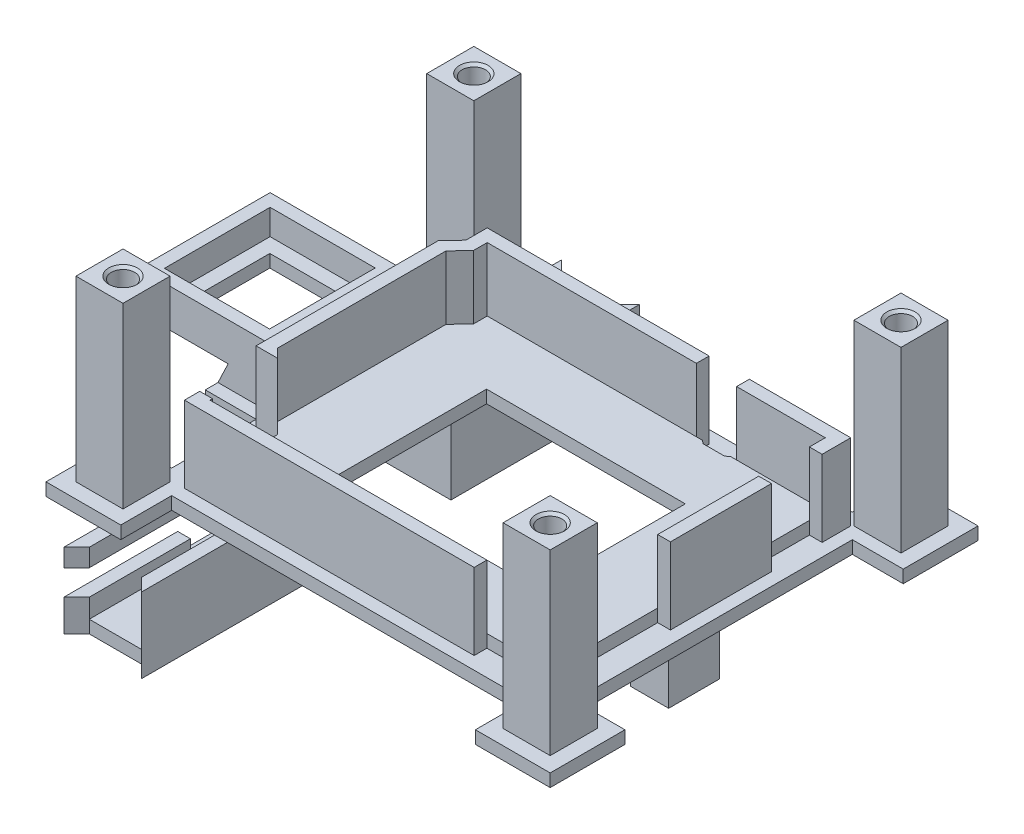
SolidWorks part; units mm, degrees
ref_plane "Front Plane" through (0, 0, 0) normal (0, 0, 1) x (1, 0, 0)
ref_plane "Top Plane" through (0, 0, 0) normal (0, 1, 0) x (1, 0, 0)
ref_plane "Right Plane" through (0, 0, 0) normal (1, 0, 0) x (0, 0, -1)
sketch "Sketch1" plane through (0, 0, 0) normal (0, -1, 0) x (1, 0, 0)
  line L0 (-32.325, 27.025) -> (34.525, 27.025)
  line L1 (34.525, 27.025) -> (34.525, -27.025)
  line L2 (34.525, -27.025) -> (-31.895, -27.025)
  line L3 (-31.895, -27.025) -> (-31.895, -24.3396)
  line L4 (-31.895, -24.3396) -> (-34.525, -21.5496)
  line L5 (-34.525, -21.5496) -> (-34.525, 11.501)
  line L6 (-34.525, 11.501) -> (-32.325, 13.751)
  line L7 (-32.325, 13.751) -> (-32.325, 27.025)
  line L8 (-32.2, 26.9) -> (34.4, 26.9) construction
  line L9 (34.4, -26.9) -> (34.4, 26.9) construction
  line L10 (16.6, -26.9) -> (34.4, -26.9) construction
  line L11 (-32.2, 13.7) -> (-32.2, 26.9) construction
  line L12 (-34.4, 11.45) -> (-32.2, 13.7) construction
  line L13 (-34.4, -21.5) -> (-34.4, 11.45) construction
  line L14 (-27.4777, 29.525) -> (37.025, 29.525)
  line L15 (37.025, 29.525) -> (37.025, -29.525)
  line L16 (37.025, -29.525) -> (-34.395, -29.525)
  line L17 (-31.77, -24.29) -> (-31.77, -26.9) construction
  line L18 (-34.4, -21.5) -> (-31.77, -24.29) construction
  line L19 (-34.395, -29.525) -> (-34.395, -25.3322)
  line L20 (-34.395, -25.3322) -> (-37.025, -22.5422)
  line L21 (-37.025, -22.5422) -> (-37.025, 14.001)
  line L22 (-37.025, 14.001) -> (-34.825, 16.251)
  line L23 (-34.825, 16.251) -> (-34.825, 29.525)
  line L24 (-34.825, 29.525) -> (-27.4777, 29.525)
  line L25 (-32.325, 26.525) -> (-34.825, 26.525)
  line L26 (9.2, -27.025) -> (17.1, -27.025)
  line L27 (9.2, -27.025) -> (9.2, -29.525)
  line L28 (9.2, -29.525) -> (17.1, -29.525)
  line L29 (17.1, -27.025) -> (17.1, -29.525)
  line L30 (-32.8139, 13.251) -> (-37.025, 13.251)
  line L32 (38.01, -14.45) -> (34.4, -14.45) construction
  line L33 (34.525, -23.9) -> (37.025, -23.9)
  line L34 (34.525, -23.9) -> (34.525, -13.95)
  line L35 (34.525, -13.95) -> (37.025, -13.95)
  line L36 (37.025, -23.9) -> (37.025, -13.95)
  line L37 (38.01, -23.4) -> (34.4, -23.4) construction
  line L38 (39.03, 17) -> (34.4, 17) construction
  line L39 (37.025, 17.5) -> (34.525, 17.5)
  line L40 (37.025, 17.5) -> (37.025, 5.9)
  line L41 (37.025, 5.9) -> (34.525, 5.9)
  line L42 (34.525, 17.5) -> (34.525, 5.9)
  line L43 (39.03, 6.4) -> (34.4, 6.4) construction
  line L44 (22.59, 26.9) -> (22.59, 22.54) construction
  line L46 (-32.325, 26.525) -> (-32.325, 16.751)
  line L48 (-34.825, 26.525) -> (-34.825, 16.751)
  line L49 (22.09, 29.525) -> (29.39, 29.525)
  line L50 (22.09, 29.525) -> (22.09, 27.025)
  line L51 (22.09, 27.025) -> (29.39, 27.025)
  line L52 (29.39, 29.525) -> (29.39, 27.025)
  line L53 (34.525, 24.8) -> (37.025, 24.8)
  line L54 (34.525, 24.8) -> (34.525, 16.8)
  line L55 (34.525, 16.8) -> (37.025, 16.8)
  line L56 (37.025, 24.8) -> (37.025, 16.8)
  line L57 (28.89, 26.9) -> (28.89, 22.54) construction
  line L58 (34.4, 24.3) -> (32.05, 24.3) construction
  line L59 (34.4, 17.3) -> (32.05, 17.3) construction
  line L72 (10.3667, -27.025) -> (11.0667, -26.5)
  line L73 (11.0667, -26.5) -> (15.2333, -26.5)
  line L74 (15.2333, -26.5) -> (15.9333, -27.025)
  line L75 (10.9, -26) -> (9.7, -26.9) construction
  line L77 (15.4, -26) -> (10.9, -26) construction
  line L79 (15.4, -26) -> (16.6, -26.9) construction
  point P72 (35.775, 24.8)
  line M6 (15.4, -26) -> (16.6, -26.9)
  line M7 (16.6, -26.9) -> (34.4, -26.9)
  line M8 (34.4, -26.9) -> (34.4, 26.9)
  line M9 (34.4, 26.9) -> (-32.2, 26.9)
  line M10 (-32.2, 26.9) -> (-32.2, 13.7)
  line M11 (-32.2, 13.7) -> (-34.4, 11.45)
  line M12 (-34.4, 11.45) -> (-34.4, -21.5)
  line M13 (-34.4, -21.5) -> (-31.77, -24.29)
  line M14 (-31.77, -24.29) -> (-31.77, -26.9)
  line M15 (-31.77, -26.9) -> (9.7, -26.9)
  line M16 (9.7, -26.9) -> (10.9, -26)
  line M17 (10.9, -26) -> (15.4, -26)
  dimension "D1" = 0.125
  dimension "D2" = 0.125
  dimension "D3" = 0.125
  dimension "D4" = 0.125
  dimension "D5" = 0.125
  dimension "D6" = 0.125
  dimension "D7" = 0.125
  dimension "D8" = 0.125
  dimension "D9" = 2.5
  dimension "D10" = 2.5
  dimension "D11" = 2.5
  dimension "D12" = 2.5
  dimension "D13" = 2.5
  dimension "D14" = 2.5
  dimension "D15" = 2.5
  dimension "D16" = 2.5
  dimension "D17" = 2.5
  dimension "D19" = 0.5
  dimension "D18" = 0.5
  dimension "D20" = 0.5
  dimension "D21" = 0.5
  dimension "D22" = 0.5
  dimension "D23" = 0.5
  dimension "D26" = 0.5
  dimension "D27" = 0.5
  dimension "D28" = 0.5
  dimension "D29" = 0.5
  dimension "D30" = 0.5
  dimension "D31" = 0.5
  dimension "D32" = 0.5
  dimension "D24" = 0.5
  dimension "D25" = 0.5
extrude "Boss-Extrude4" add sketch "Sketch1" along normal blind 2.5 contours L7 L23 L22 L21 L20 L19 L16 L27 L2 L3 L4 L5 L6 | L7 L0 L1 L39 L15 L14 L24 L23 | L33 L1 L2 L29 L16 L15 | L15 L41 L1 L35 | L1 L53 L15 L14 L52 L0 | M17 M6 M7 M8 M9 M10 M11 M12 M13 M14 M15 M16 | L7 L6 L5 L4 L3 L2 L1 L42 L0 M6 M17 M16 M15 M14 M13 M12 M11 M10 M9 M8 M7 region at (-6.6044, 0, 28.2619) region at (-5.1175, 0, 26.9373) region at (33.7869, 0, 27.7419) region at (-34.1198, 0, 12.8163) region at (35.775, 0, -4.025) region at (28.2437, 0, -27.8937) region at (0.3648, 0, -0.0614)
extrude "Boss-Extrude5" add sketch "Sketch1<5>" against normal blind 12.5 contours L24 L23 L22 L21 L20 L19 L16 L15 L14 L6 L7 L0 L1 L2 L3 L4 L5 | L50 L14 L24 L23 L25 L7 L0 | L1 L53 L15 L14 L52 L0 | L15 L41 L1 L35 | L33 L1 L2 L29 L16 L15 region at (-6.6044, 0, 28.2619) region at (33.7869, 0, 27.7419) region at (-34.1198, 0, 12.8163) region at (35.775, 0, -4.025) region at (28.2437, 0, -27.8937)
sketch "Sketch1<5>" plane through (0, 0, 0) normal (0, -1, 0) x (1, 0, 0) same geometry as "Sketch1"
sketch "Sketch2" plane through (0, 0, 0) normal (0, 1, 0) x (1, 0, 0)
  line L22 (22.09, -24.525) -> (29.39, -24.525)
  line L23 (22.09, -24.525) -> (29.39, -24.525)
  line L24 (17.1, 24.525) -> (16.7667, 24.525)
  line L25 (17.1, 24.525) -> (16.7667, 24.525)
  line L26 (9.2, 24.525) -> (-29.395, 24.525)
  line L27 (9.2, 24.525) -> (-29.395, 24.525)
  line L28 (-31.0264, -11.5032) -> (-29.825, -12.7318)
  line L29 (-31.0264, -11.5032) -> (-29.825, -12.7318)
  line L30 (32.025, 13.95) -> (32.025, 23.9)
  line L31 (32.025, 13.95) -> (32.025, 23.9)
  line L32 (32.025, 23.9) -> (32.025, 24.525)
  line L33 (32.025, 23.9) -> (32.025, 24.525)
  line L34 (32.025, 24.525) -> (17.1, 24.525)
  line L35 (32.025, 24.525) -> (17.1, 24.525)
  line L36 (-29.825, -24.525) -> (22.09, -24.525)
  line L37 (-29.825, -24.525) -> (22.09, -24.525)
  line L38 (32.025, -24.525) -> (32.025, -5.9)
  line L39 (32.025, -24.525) -> (32.025, -5.9)
  line L40 (32.025, -5.9) -> (32.025, 13.95)
  line L41 (32.025, -5.9) -> (32.025, 13.95)
  line L181 (29.39, -24.525) -> (32.025, -24.525)
  line L184 (16.7667, 24.525) -> (16.0667, 24)
  line L185 (16.0667, 24) -> (10.2333, 24)
  line L186 (10.2333, 24) -> (9.5333, 24.525)
  line L187 (9.5333, 24.525) -> (9.2, 24.525)
  line L188 (-29.395, 24.525) -> (-29.395, 23.3471)
  line L190 (-29.395, 23.3471) -> (-32.025, 20.5571)
  line L191 (-32.025, 20.5571) -> (-32.025, -10.4818)
  line L192 (-32.025, -10.4818) -> (-31.0264, -11.5032)
  line L193 (-29.825, -12.7318) -> (-29.825, -24.525)
  line L195 (29.39, -24.525) -> (32.025, -24.525)
  line L198 (16.7667, 24.525) -> (16.0667, 24)
  line L199 (16.0667, 24) -> (10.2333, 24)
  line L200 (10.2333, 24) -> (9.5333, 24.525)
  line L201 (9.5333, 24.525) -> (9.2, 24.525)
  line L202 (-29.395, 24.525) -> (-29.395, 23.3471)
  line L204 (-29.395, 23.3471) -> (-32.025, 20.5571)
  line L205 (-32.025, 20.5571) -> (-32.025, -10.4818)
  line L206 (-32.025, -10.4818) -> (-31.0264, -11.5032)
  line L207 (-29.825, -12.7318) -> (-29.825, -24.525)
  line L209 (-19.525, -14.525) -> (19.525, -14.525)
  line L210 (-19.525, -14.525) -> (-19.525, 14.525)
  line L211 (-19.525, 14.525) -> (19.525, 14.525)
  line L212 (19.525, -14.525) -> (19.525, 14.525)
  line L213 (-19.525, -14.525) -> (19.525, 14.525) construction
  line L214 (-19.525, 14.525) -> (19.525, -14.525) construction
  point P2 (0, 0)
  dimension "D1" = 2.5
extrude "Cut-Extrude1" cut sketch "Sketch2" against normal blind 12.5 contours L209 L212 L211 L210 region at (0, 0, 0)
sketch "Sketch3" plane through (0, 0, 0) normal (0, 1, 0) x (1, 0, 0)
  line L12 (-41.9, -5.7344) -> (-41.9, 15.0256)
  line L13 (-41.9, 15.0256) -> (-62.55, 15.0256)
  line L14 (-62.55, 15.0256) -> (-62.55, -5.7344)
  line L15 (-62.55, -5.7344) -> (-41.9, -5.7344)
  line L16 (-41.9, -5.7344) -> (-41.9, 15.0256)
  line L17 (-41.9, 15.0256) -> (-62.55, 15.0256)
  line L18 (-62.55, 15.0256) -> (-62.55, -5.7344)
  line L19 (-62.55, -5.7344) -> (-41.9, -5.7344)
  line L24 (-39.4, -8.2344) -> (-39.4, 17.5256)
  line L25 (-39.4, 17.5256) -> (-65.05, 17.5256)
  line L26 (-65.05, 17.5256) -> (-65.05, -8.2344)
  line L27 (-65.05, -8.2344) -> (-39.4, -8.2344)
  line L28 (-39.4, -8.2344) -> (-39.4, 17.5256)
  line L29 (-39.4, 17.5256) -> (-65.05, 17.5256)
  line L30 (-65.05, 17.5256) -> (-65.05, -8.2344)
  line L31 (-65.05, -8.2344) -> (-39.4, -8.2344)
  dimension "D1" = 0.125
  dimension "D2" = 2.625
extrude "Boss-Extrude6" add sketch "Sketch3" along normal up to surface (4.175 mm away) separate body contours L18 L19 L16 L17 | L30 L31 L28 L29 L19 L18 L17 L16 region at (-52.225, 0, -4.6456) region at (-52.225, 0, 7.8709)
extrude "Boss-Extrude7" add sketch "Sketch3<3>" along normal blind 9.17
sketch "Sketch3<3>" plane through (0, 0, 0) normal (0, 1, 0) x (1, 0, 0) same geometry as "Sketch3"
sketch "Sketch5" plane through (0, 0, 0) normal (0, -1, 0) x (1, 0, 0)
  line L1 (-65.05, 8.2344) -> (-39.4, 8.2344)
  line L2 (-65.05, 8.2344) -> (-65.05, -17.5256)
  line L3 (-65.05, -17.5256) -> (-39.4, -17.5256)
  line L4 (-39.4, 8.2344) -> (-39.4, -17.5256)
extrude "Cut-Extrude2" cut sketch "Sketch5" against normal blind 1.68
sketch "Sketch6" plane through (0, 1.68, 0) normal (0, -1, 0) x (1, 0, 0)
  line L0 (-65.05, -4.6456) -> (-39.4, -4.6456) construction
  line L1 (-59.725, -12.1456) -> (-44.725, -12.1456)
  line L2 (-59.725, -12.1456) -> (-59.725, 2.8544)
  line L3 (-59.725, 2.8544) -> (-44.725, 2.8544)
  line L4 (-44.725, -12.1456) -> (-44.725, 2.8544)
  line L5 (-59.725, -12.1456) -> (-44.725, 2.8544) construction
  line L6 (-59.725, 2.8544) -> (-44.725, -12.1456) construction
  line L7 (-65.05, 8.2344) -> (-65.05, -17.5256) construction
  line L8 (-39.4, -17.5256) -> (-39.4, 8.2344) construction
  line L9 (-52.225, 8.2344) -> (-52.225, -17.5256) construction
  line L10 (-39.4, 8.2344) -> (-65.05, 8.2344) construction
  line L11 (-65.05, -17.5256) -> (-39.4, -17.5256) construction
  point P0 (-52.225, -4.6456)
  point P18 (-52.225, -4.6456)
  dimension "D1" = 15
extrude "Cut-Extrude3" cut sketch "Sketch6" against normal up to next (2.495 mm away)
sketch "Sketch7" plane through (-39.4, 0, 0) normal (1, 0, 0) x (0, 0, -1)
  line L0 (-8.2344, 9.17) -> (17.5256, 9.17) construction
  line L1 (-8.2344, 9.17) -> (17.5256, 9.17)
  line L2 (-8.2344, 9.17) -> (-8.2344, 1.68)
  line L3 (-8.2344, 1.68) -> (17.5256, 1.68)
  line L4 (17.5256, 9.17) -> (17.5256, 1.68)
  line L5 (-8.2344, 9.17) -> (-8.2344, 1.68) construction
extrude "Boss-Extrude8" add sketch "Sketch7" along normal up to next
sketch "Sketch8" plane through (0, -2.5, 0) normal (0, -1, 0) x (1, 0, 0)
  line L31 (-34.825, 29.525) -> (22.09, 29.525) construction
  line L32 (-49.525, -42.025) -> (49.525, -42.025)
  line L33 (-49.525, -42.025) -> (-49.525, 42.025)
  line L34 (-49.525, 42.025) -> (49.525, 42.025)
  line L35 (49.525, -42.025) -> (49.525, 42.025)
  line L36 (-49.525, -42.025) -> (49.525, 42.025) construction
  line L37 (-49.525, 42.025) -> (49.525, -42.025) construction
  line L39 (37.025, 5.9) -> (37.025, -13.95) construction
  line L40 (19.525, 14.525) -> (-19.525, 14.525) construction
  line L41 (-24.525, 19.525) -> (24.525, 19.525)
  line L42 (-24.525, 19.525) -> (-24.525, -19.525)
  line L43 (-24.525, -19.525) -> (24.525, -19.525)
  line L44 (24.525, 19.525) -> (24.525, -19.525)
  line L45 (-24.525, 19.525) -> (24.525, -19.525) construction
  line L46 (-24.525, -19.525) -> (24.525, 19.525) construction
  line L47 (19.525, -14.525) -> (19.525, 14.525) construction
  point P2 (0, 0)
  point P7 (0, 0)
  dimension "D1" = 12.5
  dimension "D2" = 12.5
  dimension "D3" = 5
  dimension "D4" = 5
extrude "Boss-Extrude10" add sketch "Sketch8" along normal blind 2.5
sketch "Sketch9" plane through (0, 0, -17.5256) normal (0, 0, -1) x (-1, 0, 0)
  line L0 (47.5344, 1.68) -> (37.025, 1.68)
  line L2 (37.025, 1.68) -> (37.025, -2.5)
  line L3 (49.525, -2.5) -> (-49.525, -2.5) construction
  line L4 (49.525, -2.5) -> (47.5344, 1.68)
  line L5 (37.025, -2.5) -> (37.025, 12.5) construction
  line L6 (37.025, -2.5) -> (49.525, -2.5)
extrude "Boss-Extrude11" add sketch "Sketch9" against normal up to surface (25.76 mm away) up to face at (-51.0375, 5.425, 8.2344)
sketch "Sketch10" plane through (0, -2.5, 0) normal (0, 1, 0) x (1, 0, 0)
  line L0 (-34.395, 29.525) -> (-34.395, 25.3322) construction
  line L1 (-46.585, 29.835) -> (-37.335, 29.835)
  line L2 (-46.585, 29.835) -> (-46.585, 39.085)
  line L3 (-46.585, 39.085) -> (-37.335, 39.085)
  line L4 (-37.335, 29.835) -> (-37.335, 39.085)
  line L5 (-46.585, 29.835) -> (-37.335, 39.085) construction
  line L6 (-46.585, 39.085) -> (-37.335, 29.835) construction
  line L7 (-49.525, 42.025) -> (-34.395, 42.025)
  line L8 (-49.525, 42.025) -> (-49.525, 26.895)
  line L9 (-49.525, 26.895) -> (-34.395, 26.895)
  line L10 (-34.395, 42.025) -> (-34.395, 26.895)
  line L11 (-41.96, 26.895) -> (-41.96, 42.025) construction
  line L12 (-49.525, 34.46) -> (-34.395, 34.46) construction
  line L13 (0, 42.025) -> (0, -42.025) construction
  line L14 (-49.525, 42.025) -> (49.525, 42.025) construction
  line L15 (49.525, -42.025) -> (-49.525, -42.025) construction
  line L16 (49.525, 0) -> (-42.025, 0) construction
  line L17 (49.525, 42.025) -> (49.525, -42.025) construction
  line L18 (-42.025, -5.6094) -> (-42.025, 14.9006) construction
  line L19 (46.585, 29.835) -> (37.335, 29.835)
  line L20 (46.585, 29.835) -> (46.585, 39.085)
  line L21 (46.585, 39.085) -> (37.335, 39.085)
  line L22 (37.335, 29.835) -> (37.335, 39.085)
  line L23 (-46.585, -29.835) -> (-37.335, -29.835)
  line L24 (-37.335, -29.835) -> (-37.335, -39.085)
  line L25 (-46.585, -39.085) -> (-37.335, -39.085)
  line L26 (-46.585, -29.835) -> (-46.585, -39.085)
  line L27 (46.585, -29.835) -> (37.335, -29.835)
  line L28 (37.335, -29.835) -> (37.335, -39.085)
  line L29 (46.585, -39.085) -> (37.335, -39.085)
  line L30 (46.585, -29.835) -> (46.585, -39.085)
  line L32 (-37.335, 39.085) -> (37.335, 39.085)
  line L33 (-37.335, 39.085) -> (-37.335, 29.835)
  line L34 (-37.335, 29.835) -> (37.335, 29.835)
  line L35 (37.335, 39.085) -> (37.335, 29.835)
  line L36 (0, 29.835) -> (0, 39.085) construction
  line L37 (-37.335, 34.46) -> (37.335, 34.46) construction
  line L38 (-37.335, -29.835) -> (37.335, -29.835)
  line L39 (-37.335, -29.835) -> (-37.335, -39.085)
  line L40 (-37.335, -39.085) -> (37.335, -39.085)
  line L41 (37.335, -29.835) -> (37.335, -39.085)
  line L42 (0, -39.085) -> (0, -29.835) construction
  line L43 (-37.335, -34.46) -> (37.335, -34.46) construction
  point P0 (-41.96, 34.46)
  point P204 (0, 34.46)
  point P209 (0, -34.46)
  point P993 (-41.96, 34.46)
  line M21 (17.1, 29.525) -> (37.025, 29.525)
  line M22 (37.025, 29.525) -> (37.025, 23.9)
  line M30 (37.025, -24.8) -> (37.025, -29.525)
  line M31 (37.025, -29.525) -> (29.39, -29.525)
  dimension "D1" = 9.25
  dimension "D2" = 9.25
extrude "Boss-Extrude12" add sketch "Sketch10" along normal blind 35 contours L1 L4 L3 L2 | L22 L19 L20 L21 M21 M22 | L30 L27 L28 L29 M30 M31 | L23 L26 L25 L24 region at (-41.96, -2.5, -34.46) region at (41.96, -2.5, -34.46) region at (-41.96, -2.5, 34.46) region at (41.96, -2.5, 34.46)
sketch "Sketch11" plane through (0, 32.5, 0) normal (0, 1, 0) x (1, 0, 0)
  line L0 (-41.96, 39.085) -> (-41.96, 29.835)
  line L1 (-46.585, 39.085) -> (-37.335, 39.085) construction
  line L2 (-46.585, 29.835) -> (-37.335, 29.835) construction
  line L3 (-44.26, 34.46) -> (-44.26, 39.085)
  line L4 (-46.585, 29.835) -> (-46.585, 39.085) construction
  line L5 (-46.585, 34.46) -> (-37.335, 34.46)
  line L6 (-37.335, 29.835) -> (-37.335, 39.085) construction
  line L7 (-81.725, 0) -> (81.725, 0) construction
  line L8 (0, 67.5081) -> (0, -67.5081) construction
  circle A0 centre (-41.96, 34.46) radius 2.3
  circle A1 centre (41.96, 34.46) radius 2.3
  circle A2 centre (41.96, -34.46) radius 2.3
  circle A3 centre (-41.96, -34.46) radius 2.3
  point P20 (0, 0)
  point P24 (0, 0)
  dimension "D1" = 4.6
extrude "Cut-Extrude5" cut sketch "Sketch11" against normal blind 6.2 contours L5 A0 L0 | L0 A0 L5 | L5 A0 L0 | L0 A0 L5 | A3 | A2 | A1 region at (-40.9838, 32.5, -35.4362) region at (-42.9362, 32.5, -35.4362) region at (-40.9838, 32.5, -33.4838) region at (-42.9362, 32.5, -33.4838) region at (41.96, 32.5, -34.46) region at (41.96, 32.5, 34.46) region at (-41.96, 32.5, 34.46)
chamfer "Chamfer3" distance 0.5 angle 45 4 edges at (41.96, 32.5, 36.76) (41.96, 32.5, -32.16) (-41.96, 32.5, -32.16) (-41.96, 32.5, 36.76)
sketch "Sketch13" plane through (0, -2.5, 0) normal (0, 1, 0) x (1, 0, 0)
  line L0 (-49.525, 42.025) -> (49.525, 42.025) construction
  line L1 (-34.835, 42.025) -> (34.835, 42.025)
  line L2 (-34.835, 42.025) -> (-34.835, 32.025)
  line L3 (-34.835, 32.025) -> (34.835, 32.025)
  line L4 (34.835, 42.025) -> (34.835, 32.025)
  line L5 (0, 32.025) -> (0, 42.025) construction
  line L6 (-34.835, 37.025) -> (34.835, 37.025) construction
  line L7 (39.525, 27.335) -> (49.525, 27.335)
  line L8 (39.525, 27.335) -> (39.525, -27.335)
  line L9 (39.525, -27.335) -> (49.525, -27.335)
  line L10 (49.525, 27.335) -> (49.525, -27.335)
  line L11 (44.525, -27.335) -> (44.525, 27.335) construction
  line L12 (39.525, 0) -> (49.525, 0) construction
  line L13 (-34.835, -32.025) -> (34.835, -32.025)
  line L14 (-34.835, -32.025) -> (-34.835, -42.025)
  line L15 (-34.835, -42.025) -> (34.835, -42.025)
  line L16 (34.835, -32.025) -> (34.835, -42.025)
  line L17 (0, -42.025) -> (0, -32.025) construction
  line L18 (-34.835, -37.025) -> (34.835, -37.025) construction
  line L19 (-49.525, -10.7344) -> (-39.525, -10.7344)
  line L20 (-49.525, -10.7344) -> (-49.525, -27.335)
  line L21 (-49.525, -27.335) -> (-39.525, -27.335)
  line L22 (-39.525, -10.7344) -> (-39.525, -27.335)
  line L23 (-44.525, -27.335) -> (-44.525, -10.7344) construction
  line L24 (-49.525, -19.0347) -> (-39.525, -19.0347) construction
  line L25 (-49.525, 27.335) -> (-39.525, 27.335)
  line L26 (-49.525, 27.335) -> (-49.525, 20.0256)
  line L27 (-49.525, 20.0256) -> (-39.525, 20.0256)
  line L28 (-39.525, 27.335) -> (-39.525, 20.0256)
  line L29 (-44.525, 20.0256) -> (-44.525, 27.335) construction
  line L30 (-49.525, 23.6803) -> (-39.525, 23.6803) construction
  line L31 (9.2, 29.525) -> (-34.395, 29.525) construction
  line L32 (-37.335, 29.835) -> (-37.335, 39.085) construction
  line L33 (37.335, 29.835) -> (37.335, 39.085) construction
  line L34 (49.525, 42.025) -> (49.525, -42.025) construction
  line L35 (46.585, 29.835) -> (37.335, 29.835) construction
  line L36 (46.585, -29.835) -> (37.335, -29.835) construction
  line L37 (37.025, 23.9) -> (37.025, 29.525) construction
  line L38 (37.335, -29.835) -> (37.335, -39.085) construction
  line L39 (-34.825, -29.525) -> (22.09, -29.525) construction
  line L40 (-37.335, -29.835) -> (-37.335, -39.085) construction
  line L41 (49.525, -42.025) -> (-49.525, -42.025) construction
  line L42 (-49.525, -42.025) -> (-49.525, -8.2344) construction
  line L43 (-37.025, 22.5422) -> (-37.025, -13.251) construction
  line L44 (-46.585, -29.835) -> (-37.335, -29.835) construction
  line L45 (-49.525, -8.2344) -> (-37.025, -8.2344) construction
  line L46 (-37.025, 17.5256) -> (-49.525, 17.5256) construction
  line L47 (-46.585, 29.835) -> (-37.335, 29.835) construction
  line L48 (-37.025, 22.5422) -> (-37.025, 17.5256) construction
  line L49 (-49.525, 17.5256) -> (-49.525, 42.025) construction
  point P80 (-44.525, 23.6803)
  point P104 (44.525, 0)
  point P116 (0, 37.025)
  point P138 (0, -37.025)
  point P155 (-44.525, -19.0347)
  dimension "D1" = 0
  dimension "D2" = 2.5
  dimension "D3" = 2.5
  dimension "D4" = 2.5
  dimension "D5" = 0
  dimension "D6" = 2.5
  dimension "D7" = 2.5
  dimension "D8" = 2.5
  dimension "D9" = 2.5
  dimension "D10" = 2.5
  dimension "D11" = 2.5
  dimension "D12" = 0
  dimension "D13" = 0
  dimension "D14" = 2.5
  dimension "D15" = 2.5
  dimension "D16" = 2.5
  dimension "D17" = 2.5
  dimension "D18" = 2.5
  dimension "D19" = 2.5
  dimension "D20" = 0
extrude "Cut-Extrude6" cut sketch "Sketch13" against normal blind 10
sketch "Sketch14" plane through (0, -5, 0) normal (0, -1, 0) x (1, 0, 0)
  line L1 (-39.15, 48.9) -> (-39.15, 11.9)
  line L2 (-39.15, 11.9) -> (-23.9, 11.9)
  line L3 (-23.9, 11.9) -> (-23.9, 48.9)
  line L8 (-39.15, -11.9) -> (-39.15, -48.9)
  line L10 (-23.9, -48.9) -> (-23.9, -11.9)
  line L11 (-23.9, -11.9) -> (-39.15, -11.9)
  line L12 (-36.65, -46.4) -> (-26.4, -46.4)
  line L13 (-26.4, -46.4) -> (-26.4, -14.4)
  line L14 (-26.4, -14.4) -> (-36.65, -14.4)
  line L15 (-36.65, -14.4) -> (-36.65, -46.4)
  line L16 (-26.4, 46.4) -> (-36.65, 46.4)
  line L17 (-36.65, 46.4) -> (-36.65, 14.4)
  line L18 (-36.65, 14.4) -> (-26.4, 14.4)
  line L19 (-26.4, 14.4) -> (-26.4, 46.4)
  line L21 (-36.65, 46.4) -> (-36.65, 14.4)
  line L22 (-36.65, 14.4) -> (-26.4, 14.4)
  line L23 (-26.4, 14.4) -> (-26.4, 46.4)
  line L25 (-26.4, -46.4) -> (-26.4, -14.4)
  line L26 (-26.4, -14.4) -> (-36.65, -14.4)
  line L27 (-36.65, -14.4) -> (-36.65, -46.4)
  line L44 (-23.9, 48.9) -> (-39.15, 48.9) construction
  line L45 (-26.4, 46.4) -> (-36.65, 46.4) construction
  line L46 (-39.15, 48.9) -> (-36.65, 46.4)
  line L47 (-26.4, 46.4) -> (-23.9, 48.9)
  line L48 (-26.4, -46.4) -> (-23.9, -48.9)
  line L49 (-39.15, -48.9) -> (-23.9, -48.9) construction
  line L50 (-36.65, -46.4) -> (-26.4, -46.4) construction
  line L51 (-36.65, -46.4) -> (-39.15, -48.9)
  dimension "D1" = 0.125
  dimension "D2" = 2.5
  dimension "D3" = 0.125
  dimension "D4" = 2.5
extrude "Boss-Extrude13" add sketch "Sketch14" along normal blind 12.25
sketch "Sketch16" plane through (0, -17.25, 0) normal (0, -1, 0) x (1, 0, 0)
  line L0 (-39.15, 48.9) -> (-36.65, 46.4)
  line L1 (-36.65, 46.4) -> (-36.65, 14.4)
  line L2 (-36.65, 14.4) -> (-26.4, 14.4)
  line L3 (-26.4, 14.4) -> (-26.4, 46.4)
  line L4 (-26.4, 46.4) -> (-23.9, 48.9)
  line L5 (-23.9, 48.9) -> (-23.9, 11.9)
  line L6 (-39.15, 11.9) -> (-23.9, 11.9) construction
  line L7 (-23.9, 11.9) -> (-23.9, 48.9) construction
  line L8 (-23.9, 11.9) -> (-39.15, 11.9)
  line L9 (-39.15, 48.9) -> (-39.15, 11.9) construction
  line L18 (-36.65, -46.4) -> (-26.4, -46.4)
  line L19 (-36.65, 46.4) -> (-26.4, 46.4)
  line L26 (-23.9, -11.9) -> (-39.15, -11.9)
  line L27 (-39.15, -11.9) -> (-39.15, -48.9)
  line L28 (-39.15, -48.9) -> (-36.65, -46.4)
  line L29 (-36.65, -46.4) -> (-36.65, -14.4)
  line L30 (-36.65, -14.4) -> (-26.4, -14.4)
  line L31 (-26.4, -14.4) -> (-26.4, -46.4)
  line L32 (-26.4, -46.4) -> (-23.9, -48.9)
  line L33 (-23.9, -48.9) -> (-23.9, -11.9)
  line L34 (-23.9, -11.9) -> (-39.15, -11.9)
  line L35 (-39.15, -11.9) -> (-39.15, -48.9)
  line L36 (-39.15, -48.9) -> (-36.65, -46.4)
  line L37 (-36.65, -46.4) -> (-36.65, -14.4)
  line L38 (-36.65, -14.4) -> (-26.4, -14.4)
  line L39 (-26.4, -14.4) -> (-26.4, -46.4)
  line L40 (-26.4, -46.4) -> (-23.9, -48.9)
  line L41 (-23.9, -48.9) -> (-23.9, -11.9)
  line M9 (-23.9, 48.9) -> (-26.4, 46.4)
  line M10 (-26.4, 46.4) -> (-26.4, 14.4)
  line M11 (-26.4, 14.4) -> (-36.65, 14.4)
  line M12 (-36.65, 14.4) -> (-36.65, 46.4)
  line M13 (-36.65, 46.4) -> (-39.15, 48.9)
  line M14 (-39.15, 48.9) -> (-39.15, 11.9)
  line M15 (-39.15, 11.9) -> (-23.9, 11.9)
  line M16 (-23.9, 11.9) -> (-23.9, 48.9)
  dimension "D1" = 0
extrude "Boss-Extrude15" add sketch "Sketch16" along normal blind 2.5 contours M16 M9 M10 M11 M12 M13 M14 M15 | L40 L41 L34 L35 L36 L37 L38 L39 | L19 M12 M11 M10 | L39 L38 L37 L18 region at (-38.183, -17.25, 47.367) region at (-31.525, -17.25, 30.4) region at (-31.525, -17.25, -30.4) region at (-38.183, -17.25, -47.367)
sketch "Sketch18" plane through (-36.525, 0, 0) normal (-1, 0, 0) x (0, 0, 1)
  line L0 (-14.525, -17.125) -> (-46.275, -17.125) construction
  line L1 (-17.525, -17.125) -> (-26.525, -17.125)
  line L2 (-17.525, -17.125) -> (-17.525, -5.125)
  line L3 (-17.525, -5.125) -> (-26.525, -5.125)
  line L4 (-26.525, -17.125) -> (-26.525, -5.125)
  line L5 (-22.025, -5.125) -> (-22.025, -17.125) construction
  line L6 (-17.525, -11.125) -> (-26.525, -11.125) construction
  line L7 (-14.525, -5.125) -> (-46.275, -5.125) construction
  line L8 (46.275, -17.125) -> (14.525, -17.125) construction
  line L9 (26.525, -17.125) -> (17.525, -17.125)
  line L10 (26.525, -17.125) -> (26.525, -5.125)
  line L11 (26.525, -5.125) -> (17.525, -5.125)
  line L12 (17.525, -17.125) -> (17.525, -5.125)
  line L13 (22.025, -5.125) -> (22.025, -17.125) construction
  line L14 (26.525, -11.125) -> (17.525, -11.125) construction
  line L15 (46.275, -5.125) -> (14.525, -5.125) construction
  line L16 (-14.525, -17.125) -> (-14.525, -5.125) construction
  line L17 (14.525, -17.125) -> (14.525, -5.125) construction
  point P232 (22.025, -11.125)
  point P292 (-22.025, -11.125)
  dimension "D1" = 3
  dimension "D2" = 3
  dimension "D3" = 12
  dimension "D4" = 12
extrude "Cut-Extrude9" cut sketch "Sketch18" along normal through all
sketch "Sketch21" plane through (-39.15, 0, 0) normal (-1, 0, 0) x (0, 0, 1)
  line L0 (-26.525, -5.125) -> (-26.525, -17.125) construction
  line L1 (-26.525, -8.5) -> (-48.9, -8.5)
  line L2 (-26.525, -8.5) -> (-26.525, -13.5)
  line L3 (-26.525, -13.5) -> (-48.9, -13.5)
  line L4 (-48.9, -8.5) -> (-48.9, -13.5)
  line L5 (-37.7125, -13.5) -> (-37.7125, -8.5) construction
  line L6 (-26.525, -11) -> (-48.9, -11) construction
  line L7 (-48.9, -19.75) -> (-48.9, -5) construction
  line L8 (-27.335, -5) -> (-42.025, -5) construction
  line L9 (26.525, -17.125) -> (26.525, -5.125) construction
  line L10 (26.525, -8.5) -> (48.9, -8.5)
  line L11 (26.525, -8.5) -> (26.525, -13.5)
  line L12 (26.525, -13.5) -> (48.9, -13.5)
  line L13 (48.9, -8.5) -> (48.9, -13.5)
  line L14 (37.7125, -13.5) -> (37.7125, -8.5) construction
  line L15 (26.525, -11) -> (48.9, -11) construction
  line L16 (48.9, -19.75) -> (48.9, -5) construction
  line L17 (48.9, -5) -> (42.025, -5) construction
  point P20 (0, 0)
  point P132 (-37.7125, -11)
  point P195 (37.7125, -11)
  dimension "D1" = 5
  dimension "D2" = 3.5
  dimension "D3" = 5
  dimension "D4" = 3.5
extrude "Cut-Extrude10" cut sketch "Sketch21" against normal up to next
sketch "Sketch22" plane through (0, 0, 56.275) normal (0, 0, 1) x (1, 0, 0)
  circle A0 centre (-31.525, -11.0625) radius 16
  circle A1 centre (-31.2344, -18.3067) radius 8.75
sketch "Sketch23" plane through (0, -5, 0) normal (0, -1, 0) x (1, 0, 0)
  line L0 (39.525, 0) -> (24.525, 0) construction
  line L1 (39.525, -27.335) -> (39.525, 27.335) construction
  line L2 (24.525, -19.525) -> (24.525, 19.525) construction
  line L4 (28.275, 5) -> (35.775, 5)
  line L5 (28.275, 5) -> (28.275, -5)
  line L6 (28.275, -5) -> (35.775, -5)
  line L7 (35.775, 5) -> (35.775, -5)
  line L8 (28.275, 5) -> (35.775, -5) construction
  line L9 (28.275, -5) -> (35.775, 5) construction
  point P8 (32.025, 0)
  dimension "D1" = 7.5
  dimension "D2" = 10
extrude "Boss-Extrude17" add sketch "Sketch23" along normal blind 11.9
equation "\"SlideClearance\"= 0.125mm"
equation "\"D5@Sketch1\"=\"SlideClearance\""
equation "\"D4@Sketch1\"=\"SlideClearance\""
equation "\"D2@Sketch1\"=\"SlideClearance\""
equation "\"D1@Sketch1\"=\"SlideClearance\""
equation "\"D3@Sketch1\"=\"SlideClearance\""
equation "\"D6@Sketch1\"=\"SlideClearance\""
equation "\"D7@Sketch1\"=\"SlideClearance\""
equation "\"D8@Sketch1\"=\"SlideClearance\""
equation "\"ShellWidth\"= 2.5mm"
equation "\"D9@Sketch1\"=\"ShellWidth\""
equation "\"D10@Sketch1\"=\"ShellWidth\""
equation "\"D11@Sketch1\"=\"ShellWidth\""
equation "\"D12@Sketch1\"=\"ShellWidth\""
equation "\"D13@Sketch1\"=\"ShellWidth\""
equation "\"D14@Sketch1\"=\"ShellWidth\""
equation "\"D15@Sketch1\"=\"ShellWidth\""
equation "\"D16@Sketch1\"=\"ShellWidth\""
equation "\"D17@Sketch1\"=\"ShellWidth\""
equation "\"OpeningGap\"= 0.5mm"
equation "\"D19@Sketch1\"=\"OpeningGap\""
equation "\"D18@Sketch1\"=\"OpeningGap\""
equation "\"D20@Sketch1\"=\"OpeningGap\""
equation "\"D21@Sketch1\"=\"OpeningGap\""
equation "\"D22@Sketch1\"=\"OpeningGap\""
equation "\"D23@Sketch1\"=\"OpeningGap\""
equation "\"D26@Sketch1\"=\"OpeningGap\""
equation "\"D27@Sketch1\"=\"OpeningGap\""
equation "\"D28@Sketch1\"=\"OpeningGap\""
equation "\"D29@Sketch1\"=\"OpeningGap\""
equation "\"D30@Sketch1\"=\"OpeningGap\""
equation "\"Chamfer\"= 0.1mm"
equation "\"D1@Sketch3\"=\"SlideClearance\""
equation "\"D2@Sketch3\"=\"SlideClearance\" + \"ShellWidth\""
